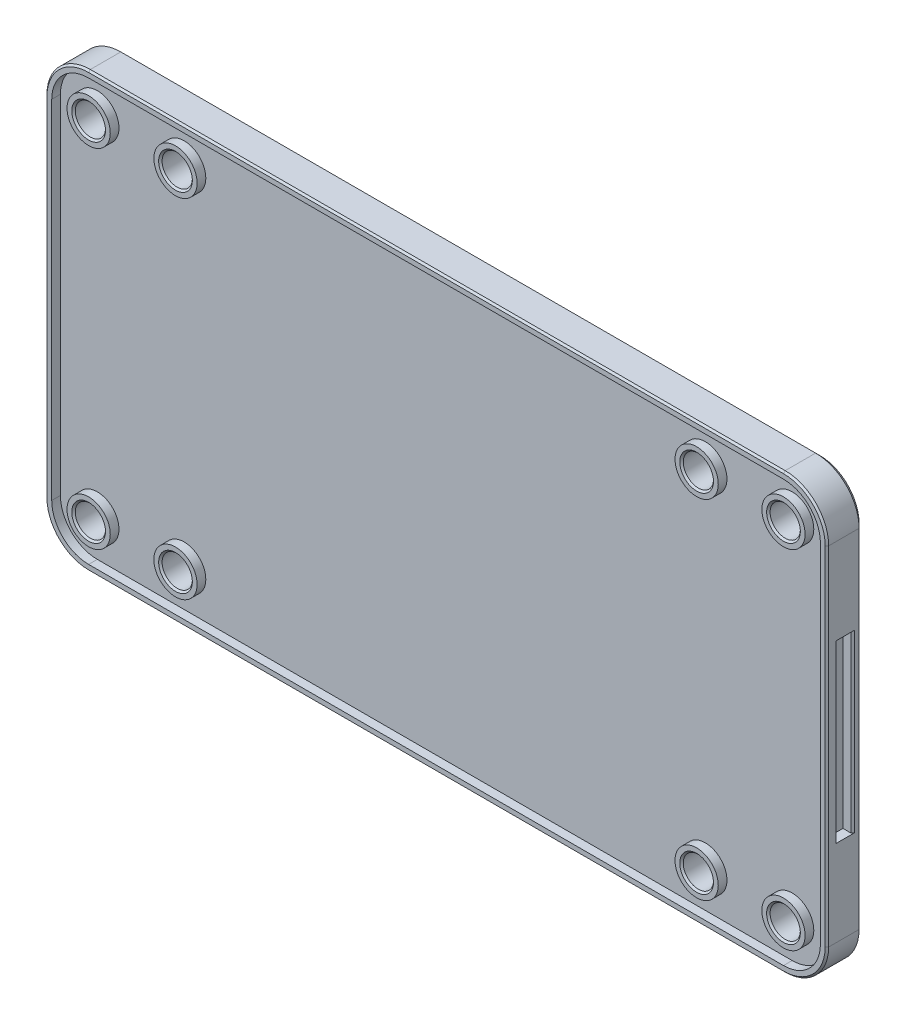
SolidWorks part; units mm, degrees
material "ABS"
ref_plane "Front Plane" through (0, 0, 0) normal (0, 0, 1) x (1, 0, 0)
ref_plane "Top Plane" through (0, 0, 0) normal (0, 1, 0) x (1, 0, 0)
ref_plane "Right Plane" through (0, 0, 0) normal (1, 0, 0) x (0, 0, -1)
sketch "Sketch1" plane through (0, 0, 0) normal (0, 0, 1) x (1, 0, 0)
  line L0 (-57.15, 0) -> (57.15, 0) construction
  line L1 (-50.8, -31.75) -> (50.8, -31.75)
  line L2 (-57.15, -25.4) -> (-57.15, 25.4)
  line L3 (-50.8, 31.75) -> (50.8, 31.75)
  line L4 (57.15, -25.4) -> (57.15, 25.4)
  line L5 (-57.15, -31.75) -> (57.15, 31.75) construction
  line L6 (-57.15, 31.75) -> (57.15, -31.75) construction
  line L7 (0, 31.75) -> (0, -31.75) construction
  arc A0 (50.8, 31.75) -> (57.15, 25.4) centre (50.8, 25.4) cw
  arc A1 (50.8, -31.75) -> (57.15, -25.4) centre (50.8, -25.4) ccw
  arc A2 (-50.8, -31.75) -> (-57.15, -25.4) centre (-50.8, -25.4) cw
  arc A3 (-57.15, 25.4) -> (-50.8, 31.75) centre (-50.8, 25.4) cw
  circle A4 centre (-50.8, -25.4) radius 2.2098
  circle A5 centre (-38.1, -25.4) radius 2.2098
  circle A6 centre (-50.8, 25.4) radius 2.2098
  circle A7 centre (-38.1, 25.4) radius 2.2098
  circle A8 centre (50.8, 25.4) radius 2.2098
  circle A9 centre (38.1, 25.4) radius 2.2098
  circle A10 centre (50.8, -25.4) radius 2.2098
  circle A11 centre (38.1, -25.4) radius 2.2098
  point P0 (0, 0)
  dimension "D3" = 6.35
  dimension "D4" = 4.4196
  dimension "D1" = 63.5
  dimension "D2" = 114.3
  dimension "D5" = 6.35
  dimension "D6" = 12.7
  dimension "D7" = 6.35
extrude "Boss-Extrude1" add sketch "Sketch1" against normal blind 3.175
sketch "Sketch2" plane through (0, 0, 0) normal (0, 0, 1) x (1, 0, 0)
  line L12 (50.8, 30.7975) -> (-50.8, 30.7975)
  line L13 (-56.1975, 25.4) -> (-56.1975, -25.4)
  line L14 (-50.8, -30.7975) -> (50.8, -30.7975)
  line L15 (56.1975, -25.4) -> (56.1975, 25.4)
  line L16 (50.8, 30.7975) -> (-50.8, 30.7975)
  line L17 (-56.1975, 25.4) -> (-56.1975, -25.4)
  line L18 (-50.8, -30.7975) -> (50.8, -30.7975)
  line L19 (56.1975, -25.4) -> (56.1975, 25.4)
  circle A0 centre (-50.8, -25.4) radius 2.2098 construction
  arc A8 (56.1975, 25.4) -> (50.8, 30.7975) centre (50.8, 25.4) ccw
  arc A9 (-50.8, 30.7975) -> (-56.1975, 25.4) centre (-50.8, 25.4) ccw
  arc A10 (-56.1975, -25.4) -> (-50.8, -30.7975) centre (-50.8, -25.4) ccw
  arc A11 (50.8, -30.7975) -> (56.1975, -25.4) centre (50.8, -25.4) ccw
  arc A12 (56.1975, 25.4) -> (50.8, 30.7975) centre (50.8, 25.4) ccw
  arc A13 (-50.8, 30.7975) -> (-56.1975, 25.4) centre (-50.8, 25.4) ccw
  arc A14 (-56.1975, -25.4) -> (-50.8, -30.7975) centre (-50.8, -25.4) ccw
  arc A15 (50.8, -30.7975) -> (56.1975, -25.4) centre (50.8, -25.4) ccw
  circle A36 centre (38.1, 25.4) radius 3.1623
  circle A37 centre (50.8, 25.4) radius 3.1623
  circle A38 centre (50.8, -25.4) radius 3.1623
  circle A39 centre (38.1, -25.4) radius 3.1623
  circle A40 centre (-38.1, -25.4) radius 3.1623
  circle A41 centre (-50.8, -25.4) radius 3.1623
  circle A42 centre (-38.1, 25.4) radius 3.1623
  circle A43 centre (-50.8, 25.4) radius 3.1623
  circle A44 centre (-38.1, -25.4) radius 2.2098 construction
  circle A47 centre (38.1, -25.4) radius 2.2098 construction
  circle A50 centre (50.8, -25.4) radius 2.2098 construction
  circle A51 centre (50.8, 25.4) radius 2.2098 construction
  circle A52 centre (38.1, 25.4) radius 2.2098 construction
  circle A53 centre (-38.1, 25.4) radius 2.2098 construction
  circle A54 centre (-50.8, 25.4) radius 2.2098 construction
  dimension "D2" = 0.9525
  dimension "D1" = 0.9525
extrude "Cut-Extrude3" cut sketch "Sketch2" against normal blind 1.27
sketch "Sketch3" plane through (0, 0, -3.175) normal (0, 0, -1) x (-1, 0, 0)
  line L4 (-57.15, 25.4) -> (-57.15, -25.4)
  line L5 (-50.8, -31.75) -> (50.8, -31.75)
  line L6 (57.15, -25.4) -> (57.15, 25.4)
  line L7 (50.8, 31.75) -> (-50.8, 31.75)
  line L8 (-57.15, 25.4) -> (-57.15, -25.4)
  line L9 (-50.8, -31.75) -> (50.8, -31.75)
  line L10 (57.15, -25.4) -> (57.15, 25.4)
  line L11 (50.8, 31.75) -> (-50.8, 31.75)
  circle A0 centre (-50.8, -25.4) radius 2.2098 construction
  circle A1 centre (-38.1, -25.4) radius 2.2098 construction
  circle A2 centre (38.1, -25.4) radius 2.2098 construction
  circle A3 centre (50.8, -25.4) radius 2.2098 construction
  arc A4 (-50.8, 31.75) -> (-57.15, 25.4) centre (-50.8, 25.4) ccw
  arc A5 (-57.15, -25.4) -> (-50.8, -31.75) centre (-50.8, -25.4) ccw
  arc A6 (50.8, -31.75) -> (57.15, -25.4) centre (50.8, -25.4) ccw
  arc A7 (57.15, 25.4) -> (50.8, 31.75) centre (50.8, 25.4) ccw
  arc A8 (-50.8, 31.75) -> (-57.15, 25.4) centre (-50.8, 25.4) ccw
  arc A9 (-57.15, -25.4) -> (-50.8, -31.75) centre (-50.8, -25.4) ccw
  arc A10 (50.8, -31.75) -> (57.15, -25.4) centre (50.8, -25.4) ccw
  arc A11 (57.15, 25.4) -> (50.8, 31.75) centre (50.8, 25.4) ccw
  circle A12 centre (50.8, 25.4) radius 2.2098 construction
  circle A13 centre (38.1, 25.4) radius 2.2098 construction
  circle A14 centre (-38.1, 25.4) radius 2.2098 construction
  circle A15 centre (-50.8, 25.4) radius 2.2098 construction
  circle A16 centre (-50.8, -25.4) radius 2.2098
  circle A17 centre (-38.1, -25.4) radius 2.2098
  circle A18 centre (38.1, -25.4) radius 2.2098
  circle A19 centre (50.8, -25.4) radius 2.2098
  circle A20 centre (50.8, 25.4) radius 2.2098
  circle A21 centre (38.1, 25.4) radius 2.2098
  circle A22 centre (-38.1, 25.4) radius 2.2098
  circle A23 centre (-50.8, 25.4) radius 2.2098
  dimension "D1" = 0
extrude "Boss-Extrude2" add sketch "Sketch3" along normal blind 2.159
sketch "Sketch4" plane through (57.15, 0, 0) normal (1, 0, 0) x (0, 0, -1)
  line L0 (5.334, -25.4) -> (0, -25.4) construction
  line L1 (1.5875, 12.827) -> (3.7465, 12.827)
  line L2 (1.5875, 12.827) -> (1.5875, -12.827)
  line L3 (1.5875, -12.827) -> (3.7465, -12.827)
  line L4 (3.7465, 12.827) -> (3.7465, -12.827)
  point P6 (2.667, -25.4)
  point P7 (2.667, -12.827)
  point P8 (1.5875, 0)
  dimension "D1" = 2.159
  dimension "D2" = 25.654
extrude "Cut-Extrude4" cut sketch "Sketch4" against normal blind 1.397
mirror "Mirror1" about plane through (0, 0, 0) normal (1, 0, 0) of "Cut-Extrude4"
sketch "Sketch5" plane through (0, 0, -5.334) normal (0, 0, -1) x (-1, 0, 0)
  circle A0 centre (0, 0) radius 12.7
  dimension "D1" = 25.4
extrude "Cut-Extrude5" cut sketch "Sketch5" against normal blind 2.54
chamfer "Chamfer1" distance 0.254 angle 45 29 edges at (48.5902, 25.4, -5.334) (-40.3098, 25.4, -5.334) (-53.0098, -25.4, -5.334) (35.8902, -25.4, -5.334) (48.5902, -25.4, -5.334) (-40.3098, -25.4, -5.334) (-53.0098, 25.4, -5.334) (35.8902, 25.4, -5.334) (-12.7, 0, -5.334) (-40.3098, 25.4, 0) (-53.0098, 25.4, 0) (-48.5902, -25.4, 0) (-35.8902, -25.4, 0) (48.5902, -25.4, 0) (35.8902, -25.4, 0) (40.3098, 25.4, 0) (53.0098, 25.4, 0) (-57.15, 0, 0) (-55.2901, -29.8901, 0) (-55.2901, 29.8901, 0) (0, -31.75, 0) (0, 31.75, 0) (55.2901, -29.8901, 0) (55.2901, 29.8901, 0) (57.15, 0, 0) (-57.15, 0, -1.5875) (-57.15, 0, -3.7465) (57.15, 0, -1.5875) (57.15, 0, -3.7465)
chamfer "Chamfer2" distance 0.635 angle 45 8 edges at (-57.15, 0, -5.334) (-55.2901, 29.8901, -5.334) (-55.2901, -29.8901, -5.334) (0, 31.75, -5.334) (0, -31.75, -5.334) (55.2901, 29.8901, -5.334) (55.2901, -29.8901, -5.334) (57.15, 0, -5.334)
equation "\"tolerance\"= 0.005"
equation "\"D4@Sketch1\"=0.164 + \"tolerance\" * 2"
equation "\"D1@Boss-Extrude2\"= 0.080000in + \"tolerance\""
equation "\"D1@Sketch4\"=0.075+ \"tolerance\" * 2"
equation "\"D2@Sketch4\" = 1 + \"tolerance\" * 2"
equation "\"D1@Cut-Extrude4\"= 0.05 + \"tolerance\""
